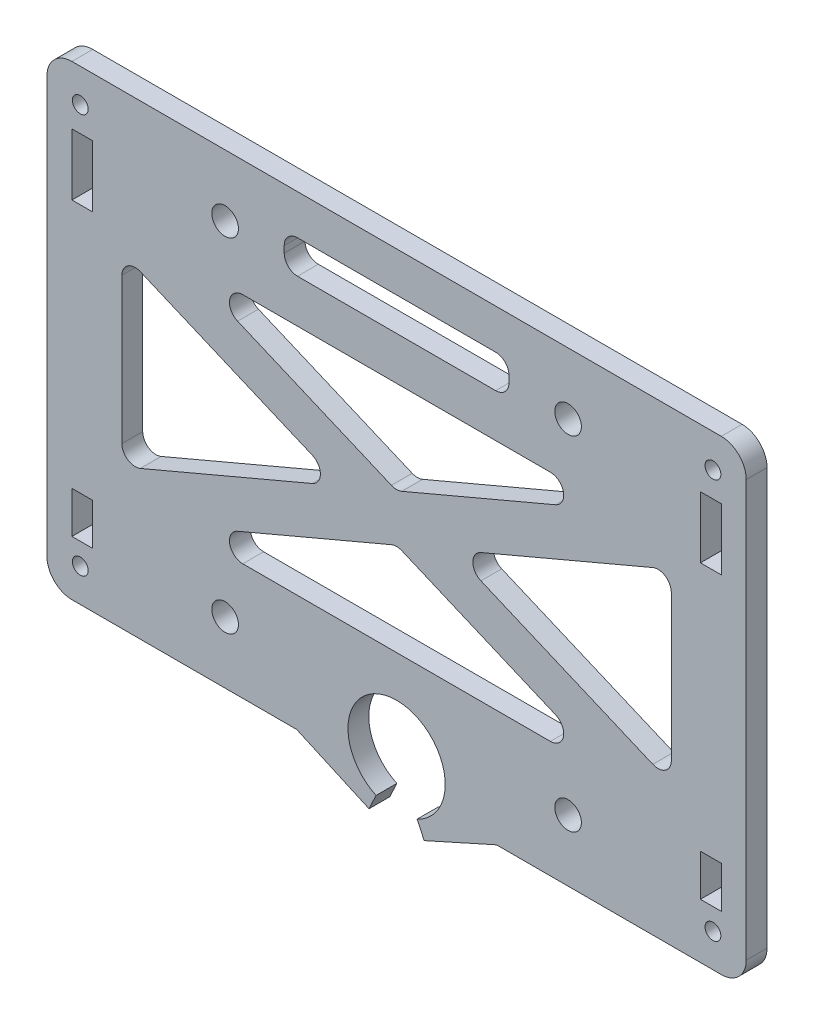
SolidWorks part; units mm, degrees
material "Delrin 2700 NC010, Low Viscosity Acetal Copolymer (SS)"
ref_plane "Front Plane" through (0, 0, 0) normal (0, 0, 1) x (1, 0, 0)
ref_plane "Top Plane" through (0, 0, 0) normal (0, 1, 0) x (1, 0, 0)
ref_plane "Right Plane" through (0, 0, 0) normal (1, 0, 0) x (0, 0, -1)
sketch "Sketch1" plane through (0, 0, 0) normal (0, 0, 1) x (1, 0, 0)
  line L0 (0, -1000) -> (0, 49000) construction
  line L1 (24.765, 17.78) -> (-24.765, 17.78)
  line L2 (26.67, 15.875) -> (26.67, -17.78)
  line L3 (26.67, -17.78) -> (-26.67, -17.78)
  line L4 (-26.67, 15.875) -> (-26.67, -17.78)
  line L5 (26.67, 17.78) -> (-26.67, -17.78) construction
  line L6 (26.67, -17.78) -> (-26.67, 17.78) construction
  line L7 (-1000, 0) -> (49000, 0) construction
  line L8 (-7.62, -17.78) -> (-2.104, -20.26)
  line L15 (-2.104, -20.26) -> (0, -15.748)
  line L16 (7.62, -17.78) -> (2.104, -20.26)
  line L17 (2.104, -20.26) -> (0, -15.748)
  line L18 (0, 0) -> (-24.2469, 20.3456) construction
  circle A0 centre (0, -15.748) radius 3.7084
  circle A1 centre (-24.13, 15.24) radius 0.6032
  circle A2 centre (-13.08, -13.08) radius 1.016
  circle A3 centre (24.13, 15.24) radius 0.6033
  circle A4 centre (-13.08, 13.08) radius 1.016
  circle A5 centre (13.08, 13.08) radius 1.016
  circle A6 centre (13.08, -13.08) radius 1.016
  arc A7 (24.765, -17.78) -> (26.67, -15.875) centre (24.765, -15.875) ccw
  arc A8 (-24.765, -17.78) -> (-26.67, -15.875) centre (-24.765, -15.875) cw
  arc A9 (-24.765, 17.78) -> (-26.67, 15.875) centre (-24.765, 15.875) ccw
  arc A10 (24.765, 17.78) -> (26.67, 15.875) centre (24.765, 15.875) cw
  circle A11 centre (24.13, -15.24) radius 0.6033
  circle A12 centre (-24.13, -15.24) radius 0.6032
  circle A13 centre (0, -15.748) radius 4.9784
  point P0 (0, 0)
  point P9 (0, 0)
  point P11 (0, -7.366)
  point P53 (-13.97, 0)
  dimension "D6" = 7.4168
  dimension "D7" = 1.2065
  dimension "D9" = 2.032
  dimension "D14" = 1.905
  dimension "D15" = 1.905
  dimension "D30" = 2.54
  dimension "D1" = 35.56
  dimension "D4" = 53.34
  dimension "D5" = 15.748
  dimension "D8" = 2.54
  dimension "D10" = 13.08
  dimension "D11" = 13.08
  dimension "D19" = 40
  dimension "D20" = 8.382
  dimension "D21" = 4
  dimension "D23" = 13.97
  dimension "D27" = 7.62
  dimension "D28" = 25
  dimension "D26" = 1.27
extrude "Boss-Extrude1" add sketch "Sketch1" along normal blind 1.5875 contours A10 L1 A9 L4 L3 A0 L2 A6 A5 A4 A1 A2 A3 | L3 A13 L15 A0 | A13 L3 L8 | L3 A13 A0 | L17 A13 L3 A0 | A13 L16 L3 region at (0, 0.4732, 0) region at (5.0756, -18.4873, 0) region at (-5.0756, -18.4873, 0) region at (2.9865, -18.87, 0) region at (3.8235, -17.6582, 0) region at (-2.9865, -18.87, 0)
ref_axis "Axis1" through (0, 0, 0) along (0, 0, 1)
sketch "Sketch2" plane through (0, 0, 1.5875) normal (0, 0, 1) x (1, 0, 0)
  line L0 (0, -1000) -> (0, 49000) construction
  line L1 (-1000, 0) -> (49000, 0) construction
  line L2 (21.0732, -7.1467) -> (-16.7276, 8.89)
  line L3 (20.955, 8.89) -> (-20.955, 8.89)
  line L4 (20.955, 8.89) -> (20.955, -8.89)
  line L5 (20.955, -8.89) -> (-20.955, -8.89)
  line L6 (-20.955, 8.89) -> (-20.955, -8.89)
  line L7 (20.955, 8.89) -> (-20.955, -8.89) construction
  line L8 (20.955, -8.89) -> (-20.955, 8.89) construction
  line L9 (16.7276, 8.89) -> (-20.955, -7.0966)
  line L10 (16.7276, -8.89) -> (-20.955, 7.0966)
  line L11 (20.955, 7.0966) -> (-16.7276, -8.89)
  line L12 (21.5998, 7.3701) -> (-20.3102, -10.4099) construction
  line L13 (20.3102, 10.4099) -> (-21.5998, -7.3701) construction
  line L14 (20.3102, -10.4099) -> (-21.5998, 7.3701) construction
  line L15 (21.5998, -7.3701) -> (-20.3102, 10.4099) construction
  line L16 (24.765, 17.78) -> (-24.765, 17.78) construction
  line L17 (8.5725, 14.732) -> (-8.5725, 14.732)
  line L18 (8.5725, 14.732) -> (8.5725, 12.192)
  line L19 (8.5725, 12.192) -> (-8.5725, 12.192)
  line L20 (-8.5725, 14.732) -> (-8.5725, 12.192)
  line L21 (8.5725, 14.732) -> (-8.5725, 12.192) construction
  line L22 (8.5725, 12.192) -> (-8.5725, 14.732) construction
  point P4 (0, 0)
  point P26 (0, 13.462)
  dimension "D3" = 17.78
  dimension "D4" = 41.91
  dimension "D5" = 3.048
  dimension "D6" = 3.302
  dimension "D7" = 17.145
  dimension "D1" = 1.651
  dimension "D2" = 1.651
extrude "Speed Holes" cut sketch "Sketch2" against normal up to next contours L9 L10 L6 | L9 L3 L2 | L4 L11 L2 | L10 L11 L5 | L17 L20 L19 L18 region at (15.3791, 0, 1.5875) region at (0, 6.5245, 1.5875) region at (0, -6.5245, 1.5875) region at (-15.3791, 0, 1.5875) region at (0, 13.462, 1.5875)
fillet "Fillet1" radius 1.016 16 edges at (-16.7276, -8.89, 0.7937) (-20.955, -7.0966, 0.7937) (0, 1.7934, 0.7937) (16.7276, -8.89, 0.7937) (20.955, -7.0966, 0.7937) (20.955, 7.0966, 0.7937) (-4.2274, 0, 0.7937) (16.7276, 8.89, 0.7937) (4.2274, 0, 0.7937) (-16.7276, 8.89, 0.7937) (0, -1.7934, 0.7937) (-20.955, 7.0966, 0.7937) (-8.5725, 14.732, 0.7937) (-8.5725, 12.192, 0.7937) (8.5725, 14.732, 0.7937) (8.5725, 12.192, 0.7937)
sketch "Sketch5" plane through (0, 0, 1.5875) normal (0, 0, 1) x (1, 0, 0)
  line L0 (24.765, 8.6264) -> (23.1775, 8.6264) construction
  line L1 (24.765, -10.4236) -> (23.1775, -10.4236) construction
  line L2 (24.765, -10.4236) -> (23.1775, -10.4236)
  line L3 (23.1775, -10.4236) -> (23.1775, -13.5986)
  line L4 (24.765, 8.6264) -> (23.1775, 8.6264)
  line L5 (23.1775, -13.5986) -> (24.765, -13.5986)
  line L6 (24.765, -13.5986) -> (24.765, -10.4236)
  line L8 (24.765, 8.6264) -> (24.765, 13.3254)
  line L9 (24.765, 13.3254) -> (23.1775, 13.3254)
  line L10 (23.1775, 13.3254) -> (23.1775, 8.6264)
  dimension "D1" = 4.699
  dimension "D2" = 3.175
extrude "Cut-Extrude1" cut sketch "Sketch5" against normal through all
mirror "Mirror1" about plane through (0, 0, 0) normal (1, 0, 0) of "Cut-Extrude1"
